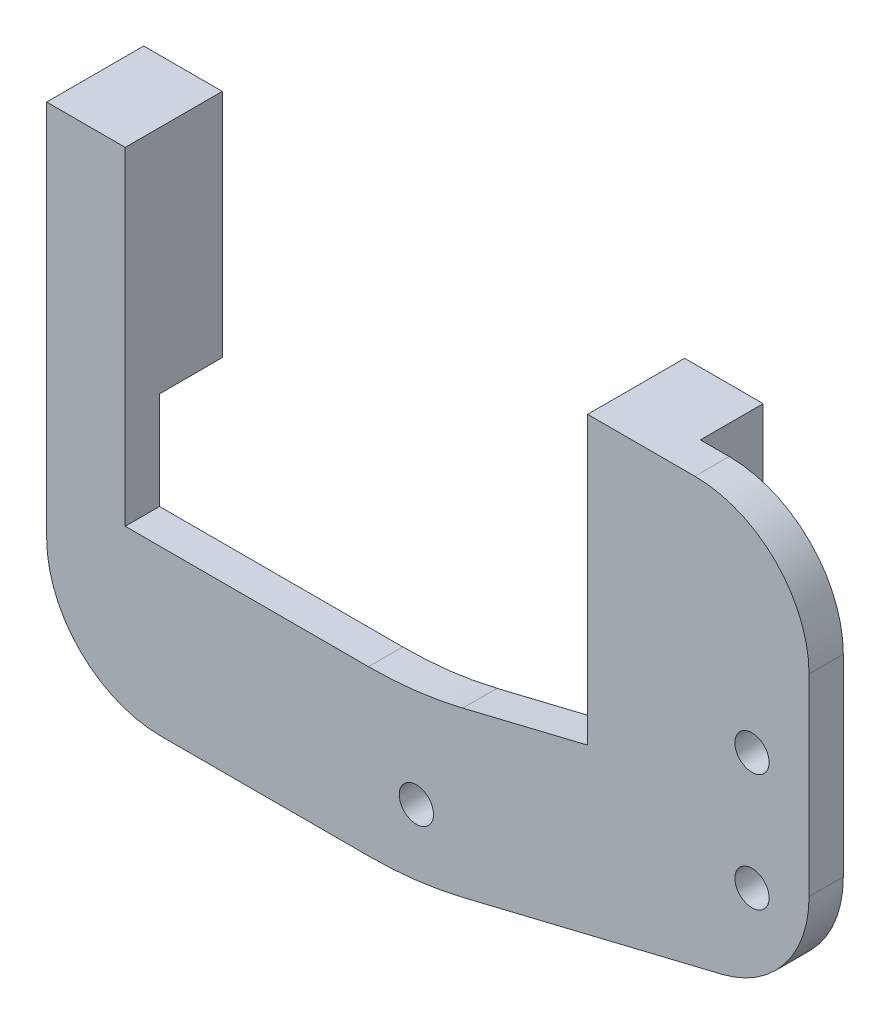
SolidWorks part; units mm, degrees
ref_plane "Alzado" through (0, 0, 0) normal (0, 0, 1) x (1, 0, 0)
ref_plane "Planta" through (0, 0, 0) normal (0, 1, 0) x (1, 0, 0)
ref_plane "Vista lateral" through (0, 0, 0) normal (1, 0, 0) x (0, 0, -1)
sketch "Croquis1" plane through (0, 0, 0) normal (0, 0, 1) x (1, 0, 0)
  line L0 (25.5, -3.4) -> (54.9, -3.4) construction
  line L1 (25.5, 10.1) -> (25.5, -16.9) construction
  line L2 (54.9, 1.74) -> (54.9, -8.54) construction
  line L3 (59.9, -14.54) -> (59.9, 20.2)
  line L4 (59.9, 20.2) -> (40.5, 20.2)
  line L5 (40.5, 20.2) -> (40.5, -4.8947)
  line L7 (0, -8.54) -> (0, 20.2)
  line L8 (0, 20.2) -> (-6.88, 20.2)
  line L9 (-6.88, 20.2) -> (-6.88, -22.9)
  line L12 (59.9, -14.54) -> (25.5, -22.9)
  line L13 (-6.88, -22.9) -> (25.5, -22.9)
  line L14 (40.5, -4.8947) -> (25.5, -8.54)
  line L15 (25.5, -8.54) -> (0, -8.54)
  circle A0 centre (54.9, 1.74) radius 1.5
  circle A1 centre (54.9, -8.54) radius 1.5
  circle A2 centre (25.5, -16.9) radius 1.5
  dimension "D4" = 3
  dimension "D5" = 5
  dimension "D6" = 6
  dimension "D7" = 6
  dimension "D1" = 10.28
  dimension "D2" = 27
  dimension "D3" = 29.4
extrude "Saliente-Extruir1" add sketch "Croquis1" along normal blind 3
sketch "Croquis2" plane through (0, 0, 0) normal (0, 0, -1) x (-1, 0, 0)
  line L1 (-40.5, 20.2) -> (-47.38, 20.2)
  line L2 (-40.5, 20.2) -> (-40.5, 0)
  line L3 (-40.5, 0) -> (-47.38, 0)
  line L4 (-47.38, 20.2) -> (-47.38, 0)
  line L5 (0, 0) -> (6.88, 0)
  line L6 (0, 0) -> (0, 20.2)
  line L7 (0, 20.2) -> (6.88, 20.2)
  line L8 (6.88, 0) -> (6.88, 20.2)
extrude "Saliente-Extruir2" add sketch "Croquis2" along normal up to surface (5.5 mm away)
fillet "Redondeo1" radius 10 3 edges at (59.9, -14.54, 1.5) (59.9, 20.2, 1.5) (-6.88, -22.9, 1.5)
fillet "Redondeo2" radius 35 2 edges at (25.5, -8.54, 1.5) (25.5, -22.9, 1.5)
